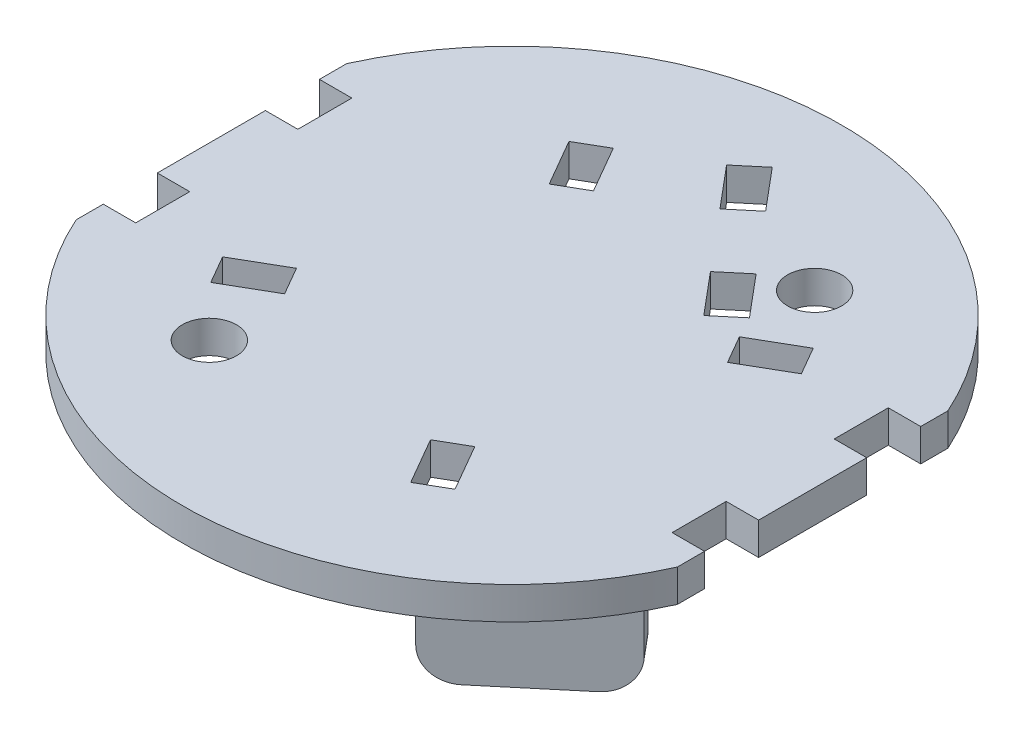
SolidWorks part; units mm, degrees
ref_plane "Alzado" through (0, 0, 0) normal (0, 0, 1) x (1, 0, 0)
ref_plane "Planta" through (0, 0, 0) normal (0, 1, 0) x (1, 0, 0)
ref_plane "Vista lateral" through (0, 0, 0) normal (1, 0, 0) x (0, 0, -1)
sketch "Croquis1" plane through (0, 0, 0) normal (0, 1, 0) x (1, 0, 0)
  circle A0 centre (0, 0) radius 30.5
extrude "Saliente-Extruir1" add sketch "Croquis1" along normal blind 3
sketch "Croquis5" plane through (0, 3, 0) normal (0, 1, 0) x (1, 0, 0)
  line L0 (0, 0) -> (0, 10)
  line L1 (28.8141, -5) -> (30.0874, -5)
  line L2 (28.8141, 5) -> (30.0874, 5)
  line L3 (-24.8141, 10) -> (-28.8141, 10)
  line L4 (24.8141, -5) -> (24.8141, -10)
  line L5 (-24.8141, -10) -> (-28.8141, -10)
  line L6 (24.8141, -5) -> (28.8141, -5)
  line L7 (24.8141, 5) -> (24.8141, 10)
  line L8 (-24.8141, 5) -> (-28.8141, 5)
  line L9 (-24.8141, 5) -> (-24.8141, 10)
  line L10 (-24.8141, -5) -> (-28.8141, -5)
  line L11 (-24.8141, -5) -> (-24.8141, -10)
  line L12 (24.8141, 5) -> (28.8141, 5)
  line L13 (24.8141, -10) -> (28.8141, -10)
  line L14 (24.8141, 10) -> (28.8141, 10)
  line L15 (-28.8141, 5) -> (-30.0874, 5)
  line L16 (-28.8141, -5) -> (-30.0874, -5)
  circle A1 centre (0, 0) radius 30.5 construction
  arc A2 (-28.8141, 10) -> (-30.0874, 5) centre (0, 0) ccw
  arc A3 (28.8141, 10) -> (28.8141, -10) centre (0, 0) cw
  arc A4 (-30.0874, -5) -> (-28.8141, -10) centre (0, 0) ccw
  arc A5 (30.0874, -5) -> (28.8141, -10) centre (0, 0) cw
  arc A6 (28.8141, 10) -> (30.0874, 5) centre (0, 0) cw
  circle M2 centre (0, 0) radius 30.5
extrude "Cortar-Extruir3" cut sketch "Croquis5" against normal blind 4 contours L11 L10 L8 L9 L3 L5 M2 | L15 L8 L9 L3 M2 | L14 L7 L12 L2 M2 | L4 L13 L1 L6 M2 region at (27.1844, 3, 7.3876) region at (27.1844, 3, -7.3876) region at (-27.1844, 3, 7.3876) region at (-27.1844, 3, -7.3876)
sketch "Croquis9" plane through (0, 3, 0) normal (0, 1, 0) x (1, 0, 0)
  line L0 (5.6733, 12.6854) -> (8.8872, 8.8552)
  line L2 (7.9714, 14.6138) -> (11.1854, 10.7835)
  line L3 (-24.8141, -5) -> (-24.8141, -10)
  line L4 (-24.8141, -10) -> (-28.8141, -10)
  line L5 (11.1854, 10.7835) -> (8.8872, 8.8552)
  line L7 (7.9714, 14.6138) -> (5.6733, 12.6854)
  line L11 (-2.1205, 21.9737) -> (1.0934, 18.1435)
  line L12 (0.1776, 23.902) -> (3.3916, 20.0718)
  line L13 (-24.8141, 10) -> (-28.8141, 10)
  line L14 (3.3916, 20.0718) -> (1.0934, 18.1435)
  line L15 (0.1776, 23.902) -> (-2.1205, 21.9737)
  arc A1 (28.8141, 10) -> (-28.8141, 10) centre (0, 0) ccw construction
  arc A5 (-28.8141, -10) -> (28.8141, -10) centre (0, 0) ccw construction
  arc A7 (-28.8141, -10) -> (22.3289, -20.7766) centre (0, 0) ccw
  arc A8 (-28.8141, 10) -> (-8.3073, 29.3469) centre (0, 0) cw
extrude "Cortar-Extruir6" cut sketch "Croquis9" against normal blind 10 contours L2 L7 | L12 L15 L14 region at (8.4293, 3, -11.7345) region at (0.6355, 3, -21.0227)
sketch "Croquis10" plane through (0, 3, 0) normal (0, 1, 0) x (1, 0, 0)
  line L0 (0, 0) -> (12, 0)
  line L1 (12, 0) -> (12, 16)
  line L2 (0, 0) -> (-12, 0)
  line L3 (-12, 0) -> (-12, -16)
  circle A0 centre (12, 16) radius 2.5
  circle A1 centre (-12, -16) radius 2.5
extrude "Cortar-Extruir7" cut sketch "Croquis10" against normal blind 10 contours A0 | A1 region at (10.2822, 3, -17.7178) region at (-10.2822, 3, 14.2822)
sketch "Croquis11" plane through (0, 3, 0) normal (0, 1, 0) x (1, 0, 0)
  line L0 (27.8141, 5) -> (30.0874, 5)
  line L1 (-27.8141, 5) -> (-27.8141, -5)
  line L2 (-24.8141, -5) -> (-30.0874, -5) construction
  line L3 (27.8141, 10) -> (28.8141, 10)
  line L4 (24.8141, 5) -> (30.0874, 5) construction
  line L5 (27.8141, 5) -> (27.8141, -5)
  line L6 (24.8141, -5) -> (30.0874, -5) construction
  line L7 (27.8141, -5) -> (30.0874, -5)
  line L8 (24.8141, 10) -> (28.8141, 10) construction
  line L9 (27.8141, 10) -> (27.8141, 12.5151)
  line L10 (27.8141, -10) -> (28.8141, -10)
  line L11 (24.8141, -10) -> (28.8141, -10) construction
  line L12 (27.8141, -10) -> (27.8141, -12.5151)
  line L13 (-28.8141, -10) -> (-27.8141, -10)
  line L14 (-24.8141, 10) -> (-28.8141, 10) construction
  line L15 (-27.8141, 10) -> (-27.8141, 12.5151)
  line L16 (-27.8141, -5) -> (-30.0874, -5)
  line L17 (-27.8141, -10) -> (-27.8141, -12.5151)
  line L18 (-27.8141, 10) -> (-28.8141, 10)
  line L19 (-30.0874, 5) -> (-27.8141, 5)
  arc A0 (28.8141, 10) -> (-28.8141, 10) centre (0, 0) ccw construction
  arc A1 (-28.8141, -10) -> (28.8141, -10) centre (0, 0) ccw construction
  arc A2 (28.8141, 10) -> (-28.8141, 10) centre (0, 0) ccw construction
  arc A3 (30.0874, -5) -> (30.0874, 5) centre (0, 0) ccw
  arc A4 (28.8141, -10) -> (27.8141, -12.5151) centre (0, 0) cw
  arc A5 (28.8141, 10) -> (27.8141, 12.5151) centre (0, 0) ccw
  arc A6 (-30.0874, -5) -> (-30.0874, 5) centre (0, 0) cw
  arc A7 (-27.8141, 12.5151) -> (-28.8141, 10) centre (0, 0) ccw
  arc A8 (-28.8141, -10) -> (-27.8141, -12.5151) centre (0, 0) ccw
  arc M11 (28.8141, 10) -> (-28.8141, 10) centre (0, 0) ccw
  line M17 (-24.8141, 5) -> (-30.0874, 5)
  arc M18 (-30.0874, 5) -> (-30.0874, -5) centre (0, 0) ccw
  line M19 (-30.0874, -5) -> (-24.8141, -5)
  arc M21 (-28.8141, -10) -> (28.8141, -10) centre (0, 0) ccw
  line M22 (28.8141, -10) -> (24.8141, -10)
  line M24 (24.8141, -5) -> (30.0874, -5)
  arc M25 (30.0874, -5) -> (30.0874, 5) centre (0, 0) ccw
  line M26 (30.0874, 5) -> (24.8141, 5)
  line M28 (24.8141, 10) -> (28.8141, 10)
  line M54 (-24.8141, -10) -> (-28.8141, -10)
  line M56 (-28.8141, 10) -> (-24.8141, 10)
extrude "Cortar-Extruir8" cut sketch "Croquis11" against normal blind 3 contours L17 M54 M21 | L1 M17 M18 M19 | L15 M56 M11 | L12 M22 M21 | L5 M26 M24 M25 | L9 M28 M11 region at (29.0914, 3, 0) region at (-29.0914, 3, 0) region at (28.1547, 3, -10.8559) region at (-28.1547, 3, -10.8559) region at (-28.1547, 3, 10.8559) region at (28.1547, 3, 10.8559)
sketch "Croquis12" plane through (0, 3, 0) normal (0, 1, 0) x (1, 0, 0)
  line L0 (18.0705, 8.701) -> (-16.5705, -11.299)
  line L1 (-8.701, 18.0705) -> (11.299, -16.5705)
  line L2 (16.5705, 11.299) -> (-18.0705, -8.701)
  line L4 (8.701, -18.0705) -> (-11.299, 16.5705)
  line L5 (10, -17.3205) -> (11.299, -16.5705)
  line L6 (10, -17.3205) -> (8.701, -18.0705)
  line L7 (-17.3205, -10) -> (-18.0705, -8.701)
  line L8 (17.3205, 10) -> (18.0705, 8.701)
  line L9 (-10, 17.3205) -> (-11.299, 16.5705)
  line L10 (-10, 17.3205) -> (-8.701, 18.0705)
  line L11 (17.3205, 10) -> (16.5705, 11.299)
  line L12 (-17.3205, -10) -> (-16.5705, -11.299)
  line L13 (-12.9904, -7.5) -> (-12.0512, -9.1268)
  line L14 (-12.9904, -7.5) -> (-13.7404, -6.201)
  line L15 (12.9904, 7.5) -> (12.2404, 8.799)
  line L16 (12.9904, 7.5) -> (13.9296, 5.8732)
  line L18 (-7.5, 12.9904) -> (-8.799, 12.2404)
  line L19 (7.5, -12.9904) -> (8.799, -12.2404)
  line L20 (7.5, -12.9904) -> (6.201, -13.7404)
  line L21 (-7.5, 12.9904) -> (-6.201, 13.7404)
  point P8 (-1.299, -0.75)
  point P17 (0.75, -1.299)
sketch "Croquis13" plane through (0, 0, 0) normal (0, -1, 0) x (1, 0, 0)
  line L0 (-6.8167, 4.322) -> (-19.6724, -10.9989)
  line L1 (-19.6724, -10.9989) -> (-17.3743, -12.9273)
  line L2 (-17.3743, -12.9273) -> (-4.5186, 2.3936)
  line L3 (-4.5186, 2.3936) -> (-6.8167, 4.322)
  line L4 (21.5273, 8.9312) -> (23.4556, 11.2293)
  line L5 (23.4556, 11.2293) -> (11.965, 20.8711)
  line L6 (11.965, 20.8711) -> (10.0366, 18.573)
  line L7 (10.0366, 18.573) -> (21.5273, 8.9312)
extrude "Saliente-Extruir2" add sketch "Croquis13" along normal blind 10
fillet "Redondeo1" radius 3 4 edges at (11.0008, -10, 19.7221) (22.4915, -10, 10.0802) (-5.6676, -10, 3.3578) (-18.5234, -10, -11.9631)
fillet "Redondeo2" radius 1 6 edges at (17.7103, 0, 16.0502) (11.0008, 0, 19.7221) (-5.6676, 0, 3.3578) (-13.2446, 0, -3.3385) (22.4915, 0, 10.0802) (-18.5234, 0, -11.9631)
extrude "Cortar-Extruir9" cut sketch "Croquis12" against normal blind 3 contours L18 L21 L1 L10 L9 L4 | L15 L16 L0 L8 L11 L2 | L19 L20 L4 L6 L5 L1 | L13 L14 L2 L7 L12 L0 region at (15.1554, 3, -8.75) region at (8.75, 3, 15.1554) region at (-15.1554, 3, 8.75) region at (-8.75, 3, -15.1554)
